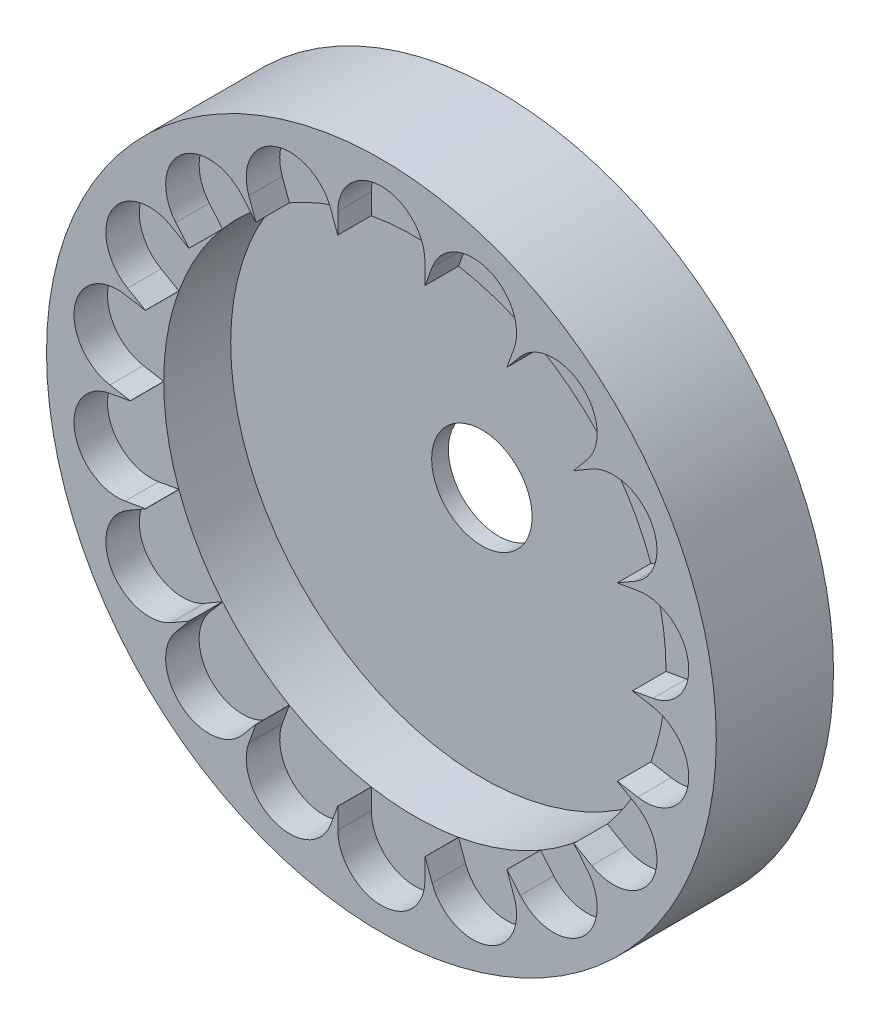
SolidWorks part; units mm, degrees
ref_plane "Front Plane" through (0, 0, 0) normal (0, 0, 1) x (1, 0, 0)
ref_plane "Top Plane" through (0, 0, 0) normal (0, 1, 0) x (1, 0, 0)
ref_plane "Right Plane" through (0, 0, 0) normal (1, 0, 0) x (0, 0, -1)
sketch "Sketch1" plane through (0, 0, 0) normal (0, 0, 1) x (1, 0, 0)
  circle A0 centre (0, 0) radius 63.5
  circle A1 centre (0, 0) radius 47.625
  dimension "D1" = 95.25
  dimension "D2" = 127
extrude "Boss-Extrude1" add sketch "Sketch1" along normal blind 19.05
sketch "Sketch2" plane through (0, 0, 19.05) normal (0, 0, 1) x (1, 0, 0)
  line L0 (0, 50.8) -> (0, -50.8) construction
  line L1 (8.255, 50.8) -> (8.255, -50.8)
  line L2 (-8.255, 50.8) -> (-8.255, -50.8)
  arc A0 (8.255, 50.8) -> (-8.255, 50.8) centre (0, 50.8) ccw
  arc A1 (-8.255, -50.8) -> (8.255, -50.8) centre (0, -50.8) ccw
  point P2 (0, 0)
  dimension "D2" = 8.255
  dimension "D1" = 101.6
extrude "Cut-Extrude1" cut sketch "Sketch2" against normal blind 6.35
pattern_circular "CirPattern1" count 10 every 20 about axis through (0, 0, 19.05) along (0, 0, -1) of "Cut-Extrude1" reverse direction yes
sketch "Sketch3" plane through (0, 0, 0) normal (0, 0, -1) x (-1, 0, 0)
  circle A0 centre (0, 0) radius 63.5
  circle A1 centre (0, 0) radius 9.525
  circle A2 centre (0, 0) radius 63.5 construction
  dimension "D1" = 19.05
extrude "Boss-Extrude2" add sketch "Sketch3" along normal blind 3.175
